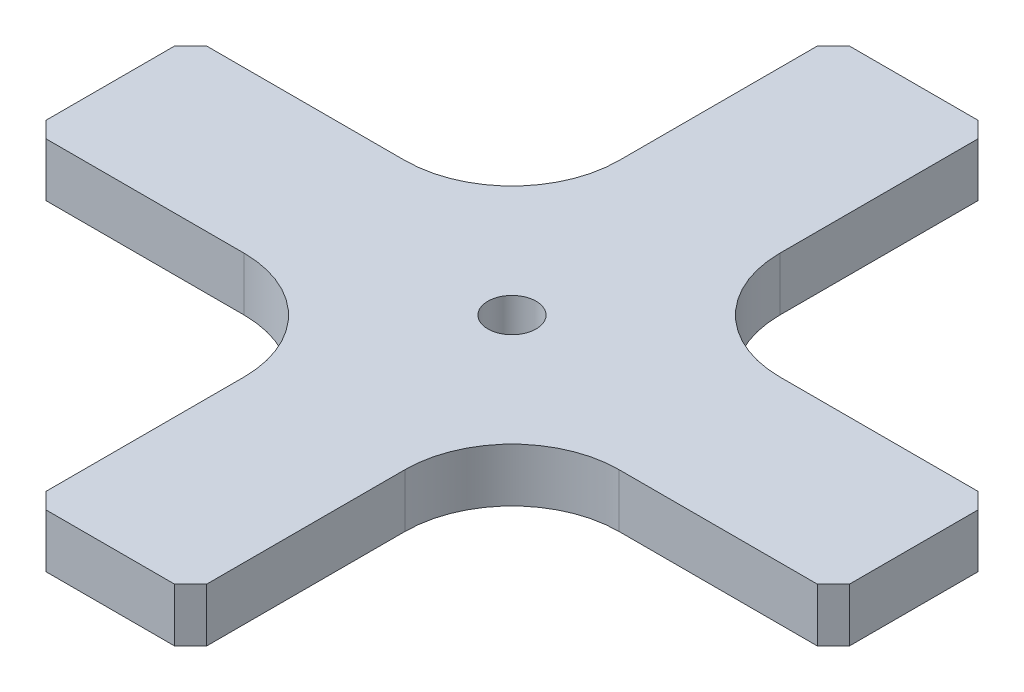
SolidWorks part; units mm, degrees
ref_plane "Front Plane" through (0, 0, 0) normal (0, 0, 1) x (1, 0, 0)
ref_plane "Top Plane" through (0, 0, 0) normal (0, 1, 0) x (1, 0, 0)
ref_plane "Right Plane" through (0, 0, 0) normal (1, 0, 0) x (0, 0, -1)
sketch "Sketch2" plane through (0, 0, 0) normal (0, 1, 0) x (1, 0, 0)
  line L0 (0, 0) -> (0, 37.5) construction
  line L1 (-7.5, 37.5) -> (7.5, 37.5)
  line L2 (7.5, 37.5) -> (7.5, 7.5)
  line L3 (0, 0) -> (7.5, 7.5) construction
  line L4 (37.5, 7.5) -> (7.5, 7.5)
  line L5 (37.5, -7.5) -> (37.5, 7.5)
  line L6 (-37.5, -7.5) -> (-37.5, 7.5)
  line L7 (-37.5, 7.5) -> (-7.5, 7.5)
  line L8 (-7.5, 37.5) -> (-7.5, 7.5)
  line L9 (0, 0) -> (-37.5, 0) construction
  line L10 (37.5, -7.5) -> (7.5, -7.5)
  line L11 (7.5, -37.5) -> (7.5, -7.5)
  line L12 (-7.5, -37.5) -> (7.5, -37.5)
  line L13 (-7.5, -37.5) -> (-7.5, -7.5)
  line L14 (-37.5, -7.5) -> (-7.5, -7.5)
  point P12 (37.5, 0)
  point P17 (-106.4691, 25.1289)
  dimension "D1" = 7.5
  dimension "D3" = 37.5
extrude "Boss-Extrude1" add sketch "Sketch2" along normal mid plane 5
fillet "Fillet1" radius 10 4 edges at (-7.5, 0, -7.5) (7.5, 0, -7.5) (7.5, 0, 7.5) (-7.5, 0, 7.5)
chamfer "Chamfer1" distance 1.5 angle 45 8 edges at (-37.5, 0, 7.5) (-37.5, 0, -7.5) (-7.5, 0, -37.5) (7.5, 0, -37.5) (37.5, 0, -7.5) (37.5, 0, 7.5) (7.5, 0, 37.5) (-7.5, 0, 37.5)
hole_wizard "M4 Clearance Hole1" positions "Sketch3" profile "Sketch4" hole size "M4" standard "ANSI Metric"
sketch "Sketch3" plane through (0, 2.5, 0) normal (0, 1, 0) x (1, 0, 0)
  point P0 (0, 0)
sketch "Sketch4" plane through (0, 2.5, 0) normal (1, 0, 0) x (0, 0, 1)
  line L0 (0, 0) -> (0, 6.5519)
  line L1 (0, 6.5519) -> (2.25, 5.2)
  line L2 (2.25, 5.2) -> (2.25, 0)
  line L5 (2.25, 0) -> (0, 0)
  line L10 (0, 6.5519) -> (-2.25, 5.2) construction
  line L11 (0, -6.35) -> (0, 107.95) construction
  dimension "Hole Dia." = 4.5
  dimension "Hole Depth" = 5.2
  dimension "Drill Angle" = 118
